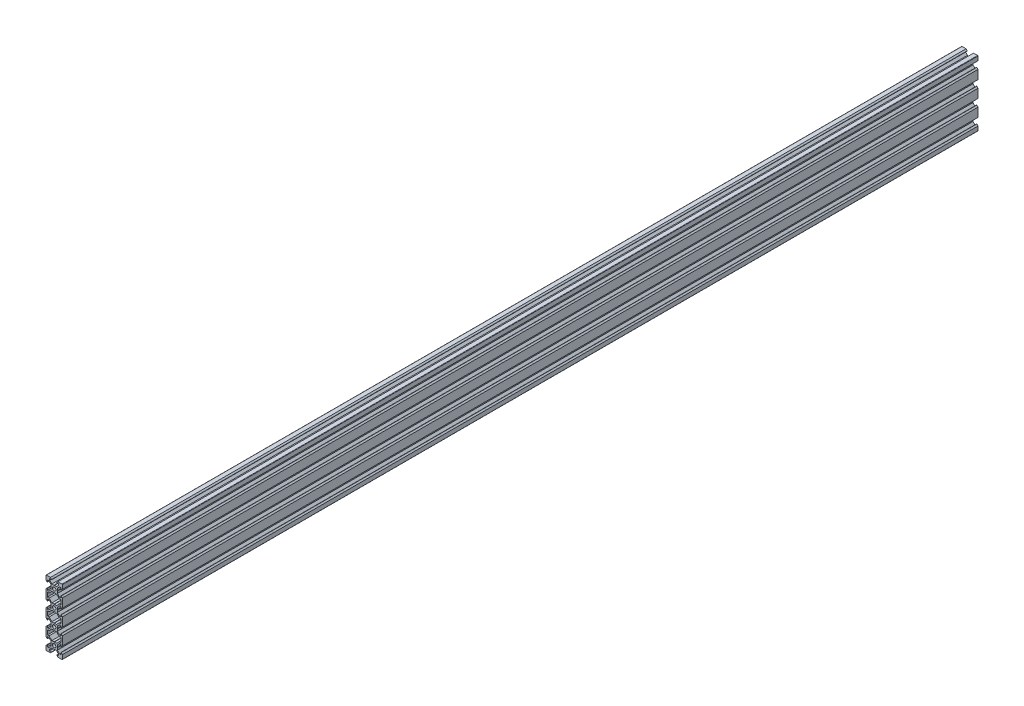
SolidWorks part; units mm, degrees
ref_plane "Plan de face" through (0, 0, 0) normal (0, 0, 1) x (1, 0, 0)
ref_plane "Plan de dessus" through (0, 0, 0) normal (0, 1, 0) x (1, 0, 0)
ref_plane "Plan de droite" through (0, 0, 0) normal (1, 0, 0) x (0, 0, -1)
ref_axis "Axe" through (0, 0, -13.782) along (0, 0, 1)
sketch "Esquisse1" plane through (0, 0, 0) normal (0, 0, 1) x (1, 0, 0)
  line L0 (0, 27.6392) -> (0, -27.6392) construction
  line L1 (-33.6074, 0) -> (33.6074, 0) construction
  line L2 (0, 0) -> (-22.2114, 22.2114) construction
  line L3 (-9.5, 10) -> (-4.58, 10)
  line L4 (-4.58, 10) -> (-3.125, 8.545)
  line L5 (-3.125, 8.545) -> (-3.125, 8.2)
  line L6 (-3.125, 8.2) -> (-5.5, 8.2)
  line L7 (-2.8393, 3.9) -> (-5.5, 6.5607)
  line L8 (-2.8393, 3.9) -> (-0.21, 3.9)
  line L9 (-5.5, 6.5607) -> (-5.5, 8.2)
  line L10 (0, 3.69) -> (0, 2.1)
  line L11 (-3.9, 2.8393) -> (-6.5607, 5.5)
  line L12 (-8.545, 3.125) -> (-8.2, 3.125)
  line L13 (-8.2, 3.125) -> (-8.2, 5.5)
  line L14 (-6.5607, 5.5) -> (-8.2, 5.5)
  line L15 (-10, 4.58) -> (-8.545, 3.125)
  line L16 (-10, 9.5) -> (-10, 4.58)
  line L17 (-0.21, 3.9) -> (0, 3.69)
  line L18 (-3.9, 2.8393) -> (-3.9, 0.21)
  line L19 (-6.2393, -12.7) -> (-8.2, -12.7)
  line L20 (-3.9, 0.21) -> (-3.69, 0)
  line L21 (-0.21, -3.9) -> (0, -3.69)
  line L22 (0, -3.69) -> (0, -2.1)
  line L23 (-6.5607, -5.5) -> (-8.2, -5.5)
  line L24 (-2.8393, -3.9) -> (-0.21, -3.9)
  line L25 (-8.545, -3.125) -> (-8.2, -3.125)
  line L26 (-10, -4.58) -> (-8.545, -3.125)
  line L27 (-8.2, -3.125) -> (-8.2, -5.5)
  line L28 (-2.8393, -3.9) -> (-6.2393, -7.3)
  line L29 (-3.9, -2.8393) -> (-6.5607, -5.5)
  line L30 (-3.9, -2.8393) -> (-3.9, -0.21)
  line L31 (-3.9, -0.21) -> (-3.69, 0)
  line L32 (-6.2393, -7.3) -> (-8.2, -7.3)
  line L33 (-8.2, -7.3) -> (-8.2, -12.7)
  line L34 (-8.2, -10) -> (-10, -10) construction
  line L35 (-10, -15.42) -> (-10, -4.58)
  line L36 (-3.9, -19.79) -> (-3.69, -20)
  line L37 (-3.9, -17.1607) -> (-3.9, -19.79)
  line L38 (-3.9, -17.1607) -> (-6.5607, -14.5)
  line L39 (-2.8393, -16.1) -> (-6.2393, -12.7)
  line L40 (-8.2, -16.875) -> (-8.2, -14.5)
  line L41 (-10, -15.42) -> (-8.545, -16.875)
  line L42 (-8.545, -16.875) -> (-8.2, -16.875)
  line L43 (-2.8393, -16.1) -> (-0.21, -16.1)
  line L44 (-6.5607, -14.5) -> (-8.2, -14.5)
  line L45 (0, -16.31) -> (0, -17.9)
  line L46 (-0.21, -16.1) -> (0, -16.31)
  line L47 (-8.2, -30) -> (-10, -30) construction
  line L48 (-3.69, -20) -> (0, -20) construction
  line L49 (-0.21, -23.9) -> (0, -23.69)
  line L50 (0, -23.69) -> (0, -22.1)
  line L51 (-6.5607, -25.5) -> (-8.2, -25.5)
  line L52 (-2.8393, -23.9) -> (-0.21, -23.9)
  line L53 (-8.545, -23.125) -> (-8.2, -23.125)
  line L54 (-10, -24.58) -> (-8.545, -23.125)
  line L55 (-8.2, -23.125) -> (-8.2, -25.5)
  line L56 (-2.8393, -23.9) -> (-6.2393, -27.3)
  line L57 (-3.9, -22.8393) -> (-6.5607, -25.5)
  line L58 (-3.9, -22.8393) -> (-3.9, -20.21)
  line L59 (-3.9, -20.21) -> (-3.69, -20)
  line L60 (-10, -24.58) -> (-10, -35.42)
  line L61 (-8.2, -32.7) -> (-8.2, -27.3)
  line L62 (-3.69, -40) -> (0, -40) construction
  line L63 (-8.2, -50) -> (-10, -50) construction
  line L64 (0, -60) -> (-22.2114, -82.2114) construction
  line L65 (-33.6074, -60) -> (33.6074, -60) construction
  line L66 (0, -87.6392) -> (0, -32.3608) construction
  line L67 (-6.2393, -32.7) -> (-8.2, -32.7)
  line L68 (-3.9, -39.79) -> (-3.69, -40)
  line L69 (-3.9, -37.1607) -> (-3.9, -39.79)
  line L70 (-3.9, -37.1607) -> (-6.5607, -34.5)
  line L71 (-2.8393, -36.1) -> (-6.2393, -32.7)
  line L72 (-8.2, -36.875) -> (-8.2, -34.5)
  line L73 (-10, -35.42) -> (-8.545, -36.875)
  line L74 (-8.545, -36.875) -> (-8.2, -36.875)
  line L75 (-6.2393, -27.3) -> (-8.2, -27.3)
  line L76 (-2.8393, -36.1) -> (-0.21, -36.1)
  line L77 (-6.5607, -34.5) -> (-8.2, -34.5)
  line L78 (0, -36.31) -> (0, -37.9)
  line L79 (-0.21, -36.1) -> (0, -36.31)
  line L80 (-0.21, -43.9) -> (0, -43.69)
  line L81 (0, -43.69) -> (0, -42.1)
  line L82 (-6.5607, -45.5) -> (-8.2, -45.5)
  line L83 (-2.8393, -43.9) -> (-0.21, -43.9)
  line L84 (-8.545, -43.125) -> (-8.2, -43.125)
  line L85 (-10, -44.58) -> (-8.545, -43.125)
  line L86 (-8.2, -43.125) -> (-8.2, -45.5)
  line L87 (-2.8393, -43.9) -> (-6.2393, -47.3)
  line L88 (-3.9, -42.8393) -> (-6.5607, -45.5)
  line L89 (-3.9, -42.8393) -> (-3.9, -40.21)
  line L90 (-3.9, -40.21) -> (-3.69, -40)
  line L91 (-10, -44.58) -> (-10, -55.42)
  line L92 (-8.2, -52.7) -> (-8.2, -47.3)
  line L93 (-6.2393, -52.7) -> (-8.2, -52.7)
  line L94 (-3.9, -59.79) -> (-3.69, -60)
  line L95 (-3.9, -57.1607) -> (-3.9, -59.79)
  line L96 (-3.9, -57.1607) -> (-6.5607, -54.5)
  line L97 (-2.8393, -56.1) -> (-6.2393, -52.7)
  line L98 (-8.2, -56.875) -> (-8.2, -54.5)
  line L99 (-10, -55.42) -> (-8.545, -56.875)
  line L100 (-8.545, -56.875) -> (-8.2, -56.875)
  line L101 (-2.8393, -56.1) -> (-0.21, -56.1)
  line L102 (-6.5607, -54.5) -> (-8.2, -54.5)
  line L103 (0, -56.31) -> (0, -57.9)
  line L104 (-0.21, -56.1) -> (0, -56.31)
  line L105 (-3.9, -60.21) -> (-3.69, -60)
  line L106 (-6.2393, -47.3) -> (-8.2, -47.3)
  line L107 (-3.9, -62.8393) -> (-3.9, -60.21)
  line L108 (-0.21, -63.9) -> (0, -63.69)
  line L109 (-10, -69.5) -> (-10, -64.58)
  line L110 (-10, -64.58) -> (-8.545, -63.125)
  line L111 (-6.5607, -65.5) -> (-8.2, -65.5)
  line L112 (-8.2, -63.125) -> (-8.2, -65.5)
  line L113 (-8.545, -63.125) -> (-8.2, -63.125)
  line L114 (-3.9, -62.8393) -> (-6.5607, -65.5)
  line L115 (0, -63.69) -> (0, -62.1)
  line L116 (-5.5, -66.5607) -> (-5.5, -68.2)
  line L117 (-2.8393, -63.9) -> (-0.21, -63.9)
  line L118 (-2.8393, -63.9) -> (-5.5, -66.5607)
  line L119 (-3.125, -68.2) -> (-5.5, -68.2)
  line L120 (-3.125, -68.545) -> (-3.125, -68.2)
  line L121 (-4.58, -70) -> (-3.125, -68.545)
  line L122 (-9.5, -70) -> (-4.58, -70)
  arc A0 (0, -2.1) -> (0, 2.1) centre (0, 0) cw
  arc A1 (-9.5, 10) -> (-10, 9.5) centre (-9.5, 9.5) ccw
  arc A2 (0, -42.1) -> (0, -37.9) centre (0, -40) cw
  arc A3 (-9.5, -70) -> (-10, -69.5) centre (-9.5, -69.5) cw
  arc A4 (0, -17.9) -> (0, -22.1) centre (0, -20) ccw
  arc A5 (0, -57.9) -> (0, -62.1) centre (0, -60) ccw
  point P4 (0, 0)
  point P7 (0, 0)
  point P30 (-10, 10)
  point P60 (0, -20)
  point P146 (-10, -70)
  dimension "D5" = 11
  dimension "D2" = 2.1
  dimension "D3" = 6.25
  dimension "D10" = 0.5
  dimension "D4" = 9.16
  dimension "D6" = 1.5
  dimension "D7" = 1.8
  dimension "D8" = 4.3
  dimension "D9" = 20
  dimension "D11" = 0.42
  dimension "D12" = 10
  dimension "D13" = 1.8
extrude "Boss.-Extru.1" add sketch "Esquisse1" along normal blind 1120
sketch "Esquisse3" plane through (0, 0, 1120) normal (0, 0, 1) x (1, 0, 0)
  line L0 (0, 0) -> (-9.8536, 9.8536) construction
  line L1 (-8.2, 8.2) -> (-8.2, 6.57)
  line L2 (-8.2, 6.57) -> (-7.54, 6.57)
  line L3 (-7.54, 6.57) -> (-6.57, 7.54)
  line L4 (-8.2, 3.125) -> (-8.2, 5.5) construction
  line L5 (-6.57, 8.2) -> (-6.57, 7.54)
  line L6 (-8.2, 8.2) -> (-6.57, 8.2)
  line L7 (-5.5, 6.5607) -> (-5.5, 8.2) construction
  line L8 (-10, -30) -> (6.918, -30) construction
  line L9 (-10, -24.58) -> (-10, -35.42) construction
  line L10 (-8.2, -68.2) -> (-6.57, -68.2)
  line L11 (-6.57, -68.2) -> (-6.57, -67.54)
  line L12 (-7.54, -66.57) -> (-6.57, -67.54)
  line L13 (-8.2, -66.57) -> (-7.54, -66.57)
  line L14 (-8.2, -68.2) -> (-8.2, -66.57)
  arc A0 (-9.5, 10) -> (-10, 9.5) centre (-9.5, 9.5) ccw construction
  point P13 (-7.055, 7.055)
  point P14 (-6.57, 7.87)
  point P26 (-7.055, -67.055)
  dimension "D1" = 1.07
extrude "Enlèv. mat.-Extru.1" [suppressed] cut sketch "Esquisse3" against normal through all
mirror "Symétrie1" about plane through (0, 3.69, 1120) normal (-1, 0, 0) of "Enlèv. mat.-Extru.1", "Boss.-Extru.1"
